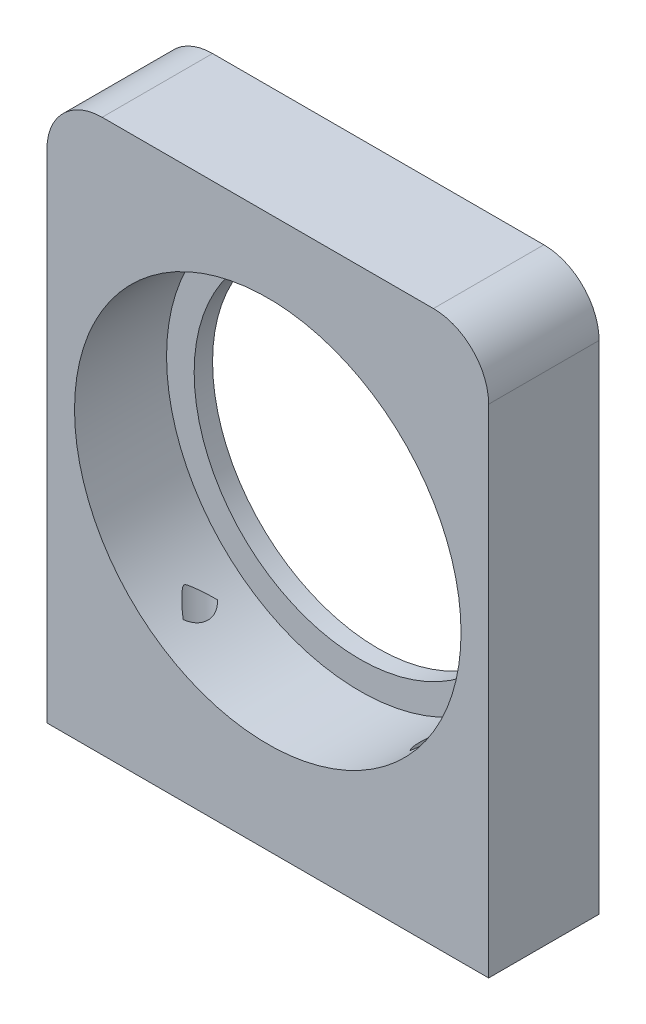
SolidWorks part; units mm, degrees
ref_plane "Ebene vorne" through (0, 0, 0) normal (0, 0, 1) x (1, 0, 0)
ref_plane "Ebene oben" through (0, 0, 0) normal (0, 1, 0) x (1, 0, 0)
ref_plane "Ebene rechts" through (0, 0, 0) normal (1, 0, 0) x (0, 0, -1)
sketch "Skizze1" plane through (0, 0, 0) normal (0, 0, 1) x (1, 0, 0)
  line L1 (-12, 30) -> (12, 30)
  line L2 (-12, 30) -> (-12, 0)
  line L3 (-12, 0) -> (12, 0)
  line L4 (12, 30) -> (12, 0)
  dimension "D1" = 24
  dimension "D2" = 30
extrude "Aufsatz-Linear austragen1" add sketch "Skizze1" along normal mid plane 6
sketch "Skizze2" plane through (0, 0, 3) normal (0, 0, 1) x (1, 0, 0)
  line L0 (0, 15.5) -> (0, 0) construction
  circle A0 centre (0, 15.5) radius 9
  circle A1 centre (0, 15.5) radius 10.5
  dimension "D1" = 21
  dimension "D2" = 18
  dimension "D3" = 15.5
extrude "Schnitt-Linear austragen2" cut sketch "Skizze2" against normal offset from surface (5 mm away) 1 contours A1 up to face at (0, 15, -3)
extrude "Schnitt-Linear austragen3" cut sketch "Skizze2<3>" against normal through all contours A0 region at (0, 15.5, 3)
sketch "Skizze2<3>" plane through (0, 0, 3) normal (0, 0, 1) x (1, 0, 0) same geometry as "Skizze2"
fillet "Verrundung1" radius 3 2 edges at (12, 30, 0) (-12, 30, 0)
hole_wizard "M3 Gewindebohrung1" positions "Skizze4" profile "Skizze5" tap size "M3" standard "DIN"
sketch "Skizze4" plane through (0, 0, 0) normal (0, -1, 0) x (-1, 0, 0)
  line L0 (7, -0.5) -> (-7, -0.5) construction
  line L1 (12, 3) -> (-12, 3) construction
  line L2 (0, -0.5) -> (0, 0) construction
  point P0 (-7, -0.5)
  point P2 (7, -0.5)
  dimension "D1" = 14
  dimension "D2" = 3.5
sketch "Skizze5" plane through (7, 0, 0.5) normal (1, 0, 0) x (0, 0, -1)
  line L0 (0, 0) -> (0, 7.7511)
  line L1 (0, 7.7511) -> (1.25, 7)
  line L2 (1.25, 7) -> (1.25, 0)
  line L5 (1.25, 0) -> (0, 0)
  line L10 (0, 7.7511) -> (-1.25, 7) construction
  line L11 (0, -6.35) -> (0, 107.95) construction
  dimension "Bohrerdurchmesser" = 2.5
  dimension "Bohrungstiefe" = 7
  dimension "Spitzenwinkel" = 118
cosmetic thread "Bohrungsgewinde1" parameters "D1"=5, "D2"=3
cosmetic thread "Bohrungsgewinde2" parameters "D1"=5, "D2"=3
